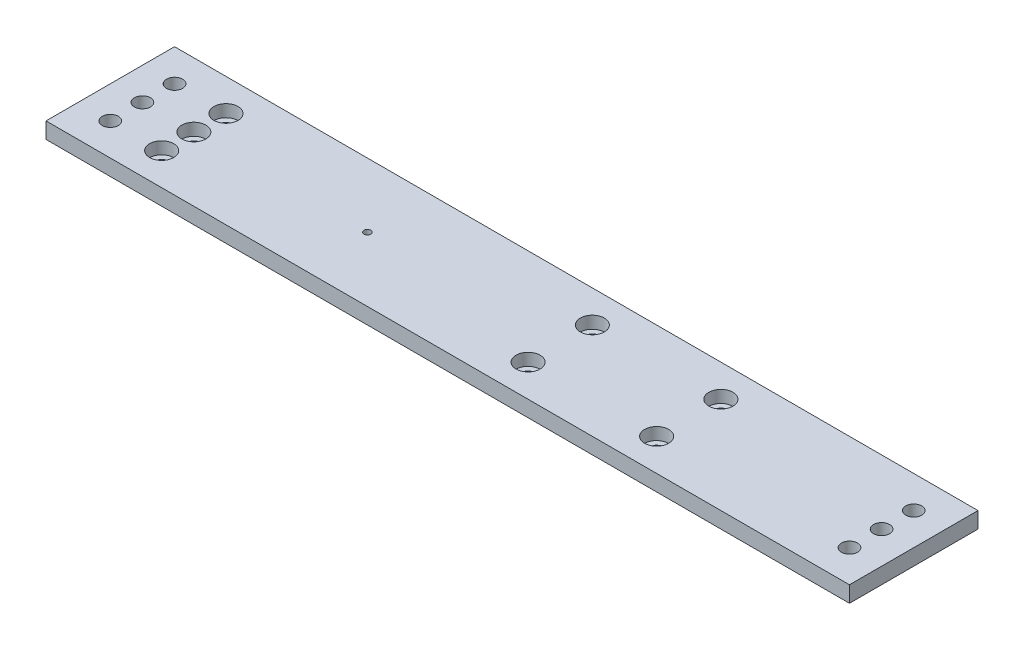
SolidWorks part; units mm, degrees
material "6061-T6 (SS)"
ref_plane "Front" through (0, 0, 0) normal (0, 0, 1) x (1, 0, 0)
ref_plane "Top" through (0, 0, 0) normal (0, 1, 0) x (1, 0, 0)
ref_plane "Right" through (0, 0, 0) normal (1, 0, 0) x (0, 0, -1)
sketch "Sketch1" plane through (0, 0, 0) normal (0, 1, 0) x (1, 0, 0)
  line L1 (-158.75, -25.4) -> (158.75, -25.4)
  line L2 (-158.75, -25.4) -> (-158.75, 25.4)
  line L3 (-158.75, 25.4) -> (158.75, 25.4)
  line L4 (158.75, -25.4) -> (158.75, 25.4)
  line L5 (-158.75, -25.4) -> (158.75, 25.4) construction
  line L6 (-158.75, 25.4) -> (158.75, -25.4) construction
  point P0 (0, 0)
  dimension "D1" = 50.8
  dimension "D2" = 317.5
extrude "Boss-Extrude1" add sketch "Sketch1" along normal blind 6.35
hole_wizard "CBORE for #10 Socket Head Cap Screw1" positions "Sketch2" profile "Sketch4" counterbore size "#10" standard "ANSI Inch" end condition through all
sketch "Sketch2" plane through (0, 6.35, 0) normal (0, 1, 0) x (1, 0, 0)
  line L2 (158.75, 25.4) -> (-158.75, 25.4) construction
  line L6 (-158.75, -25.4) -> (158.75, -25.4) construction
  line L8 (-158.75, 25.4) -> (-158.75, -25.4) construction
  line L12 (158.75, -25.4) -> (158.75, 25.4) construction
  line L15 (19.05, 12.7) -> (19.05, 25.4) construction
  line L17 (19.05, -12.7) -> (19.05, -25.4) construction
  line L18 (-125.73, -25.4) -> (-125.73, -12.7) construction
  line L20 (-125.73, 0) -> (-125.73, 12.7) construction
  line L21 (-125.73, 12.7) -> (-125.73, 25.4) construction
  line L22 (-125.73, 0) -> (-125.73, -12.7) construction
  point P64 (19.05, 12.7)
  point P66 (69.85, 12.7)
  point P68 (19.05, -12.7)
  point P70 (69.85, -12.7)
  point P92 (-125.73, 12.7)
  point P94 (-125.73, 0)
  point P102 (-125.73, -12.7)
  dimension "D2" = 50.8
  dimension "D3" = 25.4
  dimension "D4" = 88.9
  dimension "D5" = 33.02
sketch "Sketch4" plane through (-125.73, 6.35, 12.7) normal (1, 0, 0) x (0, 0, 1)
  line L0 (0, 0) -> (0, 6.35)
  line L1 (0, 6.35) -> (2.5527, 6.35)
  line L3 (2.5527, 6.35) -> (2.5527, 4.826)
  line L4 (2.5527, 4.826) -> (4.7625, 4.826)
  line L5 (4.7625, 4.826) -> (4.7625, 0)
  line L7 (4.7625, 0) -> (0, 0)
  line L11 (0, -6.35) -> (0, 107.95) construction
  dimension "Thru Hole Dia." = 5.1054
  dimension "Thru Hole Depth" = 6.35
  dimension "C'Bore Dia." = 9.525
  dimension "C'Bore Depth" = 4.826
sketch "Sketch7" plane through (0, 0, 0) normal (0, -1, 0) x (1, 0, 0)
  line L0 (-146.05, 25.4) -> (-146.05, 12.7) construction
  line L1 (-158.75, 25.4) -> (158.75, 25.4) construction
  line L2 (-146.05, 12.7) -> (-146.05, 0) construction
  line L3 (-146.05, 0) -> (-146.05, -12.7) construction
  line L4 (-146.05, -12.7) -> (-146.05, -25.4) construction
  line L5 (158.75, -25.4) -> (-158.75, -25.4) construction
  line L7 (-158.75, -25.4) -> (-158.75, 25.4) construction
  line L8 (146.05, 25.4) -> (146.05, 12.7) construction
  line L9 (146.05, 12.7) -> (146.05, 0) construction
  line L10 (146.05, 0) -> (146.05, -12.7) construction
  line L11 (146.05, -12.7) -> (146.05, -25.4) construction
  line L13 (158.75, 25.4) -> (158.75, -25.4) construction
  point P0 (-146.05, 12.7)
  point P2 (-146.05, 0)
  point P4 (-146.05, -12.7)
  point P6 (146.05, 12.7)
  point P8 (146.05, 0)
  point P10 (146.05, -12.7)
  dimension "D1" = 12.7
  dimension "D2" = 12.7
hole_wizard "1/4 (0.25) Diameter Hole1" positions "Sketch7" profile "Sketch6" hole size "1/4" standard "ANSI Inch" end condition through all
sketch "Sketch6" plane through (-146.05, 0, 12.7) normal (1, 0, 0) x (0, 0, -1)
  line L0 (0, 0) -> (0, 6.35)
  line L1 (0, 6.35) -> (3.175, 6.35)
  line L2 (3.175, 6.35) -> (3.175, 0)
  line L5 (3.175, 0) -> (0, 0)
  line L11 (0, -6.35) -> (0, 107.95) construction
  dimension "Thru Hole Dia." = 6.35
  dimension "Thru Hole Depth" = 6.35
sketch "Sketch10" plane through (0, 0, 0) normal (0, -1, 0) x (-1, 0, 0)
  line L0 (158.75, 25.4) -> (158.75, -25.4) construction
  point P0 (57.15, 0)
  dimension "D1" = 101.6
hole_wizard "#6-32 Tapped Hole1" positions "Sketch10" profile "Sketch9" tap size "#6-32" standard "ANSI Inch" end condition through all
sketch "Sketch9" plane through (-57.15, 0, 0) normal (1, 0, 0) x (0, 0, -1)
  line L0 (0, 0) -> (0, 6.35)
  line L1 (0, 6.35) -> (1.3525, 6.35)
  line L2 (1.3525, 6.35) -> (1.3525, 0)
  line L5 (1.3525, 0) -> (0, 0)
  line L11 (0, -6.35) -> (0, 107.95) construction
  dimension "Thru Tap Drill Dia." = 2.7051
  dimension "Thru Tap Drill Depth" = 6.35
cosmetic thread "Hole Thread1" parameters "D2"=3.5052
sketch "Sketch11" plane through (0, 0, 0) normal (0, -1, 0) x (1, 0, 0)
  line L0 (158.75, -25.4) -> (-158.75, -25.4) construction
  line L1 (-70.0118, -25.4) -> (-48.1024, -25.4)
  line L2 (-70.0118, -25.4) -> (-70.0118, -45.81)
  line L3 (-70.0118, -45.81) -> (-48.1024, -45.81)
  line L4 (-48.1024, -25.4) -> (-48.1024, -45.81)
extrude "Boss-Extrude2" [suppressed] add sketch "Sketch11" against normal up to surface (6.35 mm away) up to face at (-57.15, 6.35, -1.3526)
